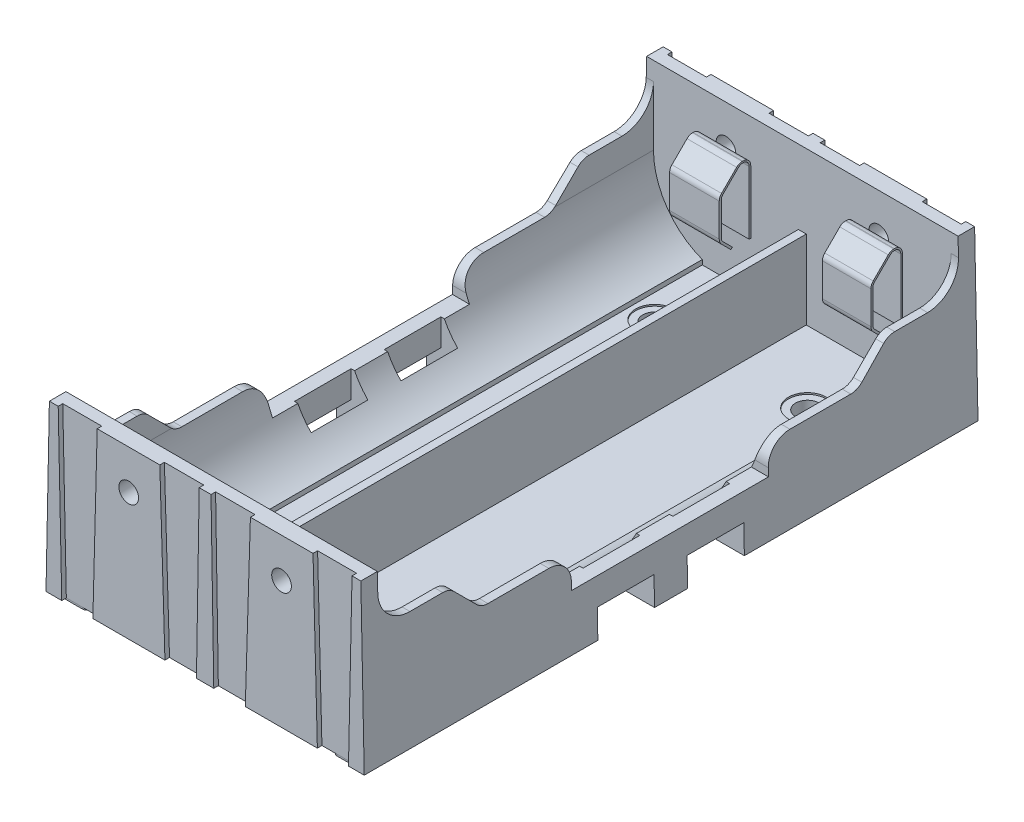
SolidWorks part; units mm, degrees
ref_plane "Plan de face" through (0, 0, 0) normal (0, 0, 1) x (1, 0, 0)
ref_plane "Plan de dessus" through (0, 0, 0) normal (0, 1, 0) x (1, 0, 0)
ref_plane "Plan de droite" through (0, 0, 0) normal (1, 0, 0) x (0, 0, -1)
sketch "Esquisse1" plane through (0, 0, 0) normal (0, 0, 1) x (1, 0, 0)
  line L0 (-20.2, 0) -> (20.2, 0)
  line L1 (20.2, 0) -> (19.9, 14.8)
  line L2 (19.9, 14.8) -> (18.9, 14.8)
  line L3 (18.9, 14.8) -> (18.9, 11.2676)
  line L4 (12.7, 1.74) -> (0.5, 1.74)
  line L5 (0.5, 1.74) -> (0.5, 11.74)
  line L6 (0.5, 11.74) -> (-0.5, 11.74)
  line L7 (0, 11.74) -> (0, 0)
  line L8 (12.7, 9.965) -> (12.7, -2.9901) construction
  line L9 (-6.3412, 2.34) -> (28.9788, 2.34) construction
  line L10 (12.7, 2.34) -> (12.7, 1.74)
  line L11 (6.3412, 2.34) -> (-28.9788, 2.34) construction
  line L12 (-12.7, 9.965) -> (-12.7, -2.9901) construction
  line L13 (-12.7, 2.34) -> (-12.7, 1.74)
  line L14 (-0.5, 1.74) -> (-0.5, 11.74)
  line L15 (-12.7, 1.74) -> (-0.5, 1.74)
  line L16 (-18.9, 14.8) -> (-18.9, 11.2676)
  line L17 (-19.9, 14.8) -> (-18.9, 14.8)
  line L18 (-20.2, 0) -> (-19.9, 14.8)
  arc A0 (-12.7, 2.34) -> (-18.9, 11.2676) centre (-9.3724, 11.2676) cw
  arc A1 (12.7, 2.34) -> (18.9, 11.2676) centre (9.3724, 11.2676) ccw
  arc A2 (12.7, 2.34) -> (18.9, 11.2676) centre (9.3724, 11.2676) ccw
  arc A3 (-12.7, 2.34) -> (-18.9, 11.2676) centre (-9.3724, 11.2676) cw
  point P15 (12.7, 2.34)
  dimension "D7" = 14.8
  dimension "D1" = 10
  dimension "D2" = 1.74
  dimension "D3" = 0.5
  dimension "D4" = 20.2
  dimension "D5" = 1
  dimension "D6" = 19.9
  dimension "D8" = 12.2
  dimension "D9" = 0.6
extrude "Boss.-Extru.1" add sketch "Esquisse1" along normal blind 73.72 contours L13 A0 L16 L17 L18 L0 L7 L6 L14 L15 | A1 L10 L4 L5 L6 L7 L0 L1 L2 L3 region at (-19.7996, 7.3949, 0) region at (0.2504, 5.87, 0)
sketch "Esquisse2" plane through (0, 0, 73.72) normal (0, 0, 1) x (1, 0, 0)
  line L0 (-20.2, 0) -> (20.2, 0)
  line L1 (20.2, 0) -> (19.7715, 21.14)
  line L2 (19.7715, 21.14) -> (-19.7715, 21.14)
  line L3 (-19.7715, 21.14) -> (-20.2, 0)
  line L4 (-20.2, 0) -> (-19.9, 14.8) construction
  line L5 (20.2, 0) -> (19.9, 14.8) construction
  dimension "D1" = 21.14
extrude "Boss.-Extru.2" add sketch "Esquisse2" along normal blind 2.1
sketch "Esquisse3" plane through (0, 0, 0) normal (0, 0, -1) x (-1, 0, 0)
  line L0 (-20.2, 0) -> (20.2, 0)
  line L1 (20.2, 0) -> (19.7715, 21.14)
  line L2 (19.7715, 21.14) -> (-19.7715, 21.14)
  line L3 (-19.7715, 21.14) -> (-20.2, 0)
extrude "Boss.-Extru.3" add sketch "Esquisse3" along normal blind 2.1
fillet "Congé1" radius 4 4 edges
sketch "Esquisse4" plane through (0, 0, 0) normal (1, 0, 0) x (0, 0, -1)
  line L0 (-64.72, 14.8) -> (-60.72, 10.8)
  line L1 (-60.72, 10.8) -> (-49.36, 10.8)
  line L2 (-49.36, 10.8) -> (-49.36, 7)
  line L3 (-49.36, 7) -> (-24.36, 7)
  line L4 (-36.86, 0) -> (-36.86, 25.0916) construction
  line L5 (-75.82, 0) -> (2.1, 0) construction
  line L6 (-64.72, 14.8) -> (-9, 14.8)
  line L7 (-69.72, 14.8) -> (-4, 14.8) construction
  line L8 (-73.72, 18.8) -> (-73.72, 21.14) construction
  line L9 (-24.36, 10.8) -> (-24.36, 7)
  line L10 (-13, 10.8) -> (-24.36, 10.8)
  line L11 (-9, 14.8) -> (-13, 10.8)
  point P15 (-36.86, 7)
  point P18 (-36.86, 14.8)
  dimension "D1" = 9
  dimension "D2" = 10.8
  dimension "D3" = 13
  dimension "D4" = 12.5
  dimension "D5" = 7
extrude "Enlèv. mat.-Extru.1" cut sketch "Esquisse4" against normal up to next and the other way through all from offset 20
extrude "Enlèv. mat.-Extru.2" cut sketch "Esquisse4<2>" along normal up to next from offset 30 offset against normal yes
sketch "Esquisse4<2>" plane through (0, 0, 0) normal (1, 0, 0) x (0, 0, -1) same geometry as "Esquisse4"
sketch "Esquisse6" plane through (0, 0, 0) normal (1, 0, 0) x (0, 0, -1)
  line L0 (-36.86, 0) -> (-36.86, 27.7538) construction
  line L1 (-46.16, -3.5482) -> (-38.96, -3.5482)
  line L2 (-46.16, -3.5482) -> (-46.16, 3.6)
  line L3 (-46.16, 3.6) -> (-38.96, 3.6)
  line L4 (-38.96, -3.5482) -> (-38.96, 3.6)
  line L5 (-75.82, 0) -> (2.1, 0) construction
  line L6 (-27.56, -3.5482) -> (-34.76, -3.5482)
  line L7 (-34.76, -3.5482) -> (-34.76, 3.6)
  line L8 (-27.56, 3.6) -> (-34.76, 3.6)
  line L9 (-27.56, -3.5482) -> (-27.56, 3.6)
  dimension "D1" = 7.2
  dimension "D2" = 4.2
  dimension "D3" = 3.6
extrude "Enlèv. mat.-Extru.3" cut sketch "Esquisse6" against normal blind 4 from vertex starting at point (20.2, 0, -2.1)
extrude "Enlèv. mat.-Extru.4" cut sketch "Esquisse6<2>" along normal blind 4 from vertex starting at point (-20.2, 0, -2.1)
sketch "Esquisse6<2>" plane through (0, 0, 0) normal (1, 0, 0) x (0, 0, -1) same geometry as "Esquisse6"
sketch "Esquisse7" plane through (0, 0, 0) normal (0, -1, 0) x (1, 0, 0)
  line L0 (0, 75.82) -> (0, 65.6835) construction
  line L1 (-20.2, 75.82) -> (20.2, 75.82) construction
  line L2 (0, 65.6835) -> (-20.2, 36.86) construction
  line L3 (-20.2, 38.96) -> (-20.2, 34.76) construction
  line L4 (-20.2, 36.86) -> (-7.0506, 36.86) construction
  line L5 (16.2, 38.96) -> (20.127, 38.96) construction
  line L6 (16.2, 46.16) -> (18.327, 46.16)
  line L7 (16.2, 46.16) -> (16.2, 38.96)
  line L8 (16.2, 38.96) -> (18.327, 38.96)
  line L9 (18.327, 46.16) -> (18.327, 38.96)
  line L10 (20.127, 46.16) -> (20.127, 38.96) construction
  line L11 (-18.327, 46.16) -> (-18.327, 38.96)
  line L12 (-16.2, 38.96) -> (-18.327, 38.96)
  line L13 (-16.2, 46.16) -> (-16.2, 38.96)
  line L14 (-16.2, 46.16) -> (-18.327, 46.16)
  line L15 (18.327, 27.56) -> (18.327, 34.76)
  line L16 (16.2, 34.76) -> (18.327, 34.76)
  line L17 (16.2, 27.56) -> (16.2, 34.76)
  line L18 (16.2, 27.56) -> (18.327, 27.56)
  line L19 (-16.2, 27.56) -> (-18.327, 27.56)
  line L20 (-16.2, 27.56) -> (-16.2, 34.76)
  line L21 (-16.2, 34.76) -> (-18.327, 34.76)
  line L22 (-18.327, 27.56) -> (-18.327, 34.76)
  dimension "D1" = 1.8
extrude "Enlèv. mat.-Extru.5" cut sketch "Esquisse7" against normal through all
fillet "Congé2" radius 2 8 edges at (-19.4, 14.8, 9) (19.4, 14.8, 9) (19.4, 14.8, 64.72) (-19.4, 14.8, 64.72) (-19.4348, 10.8, 60.72) (19.4348, 10.8, 60.72) (19.4348, 10.8, 13) (-19.4348, 10.8, 13)
fillet "Congé3" radius 2.8 4 edges at (19.4348, 10.8, 49.36) (19.4348, 10.8, 24.36) (-19.4348, 10.8, 24.36) (-19.4348, 10.8, 49.36)
sketch "Esquisse8" plane through (0, 0, 0) normal (0, -1, 0) x (1, 0, 0)
  line L0 (0, 75.82) -> (0, 59.6199) construction
  line L1 (-20.2, 75.82) -> (20.2, 75.82) construction
  line L2 (0, 59.6199) -> (-20.2, 36.86) construction
  line L3 (-20.2, 38.96) -> (-20.2, 34.76) construction
  line L4 (-20.2, 36.86) -> (-10.1, 36.86) construction
  line L5 (-20.2, 75.82) -> (-20.2, 46.16) construction
  line L6 (-19.1, 75.22) -> (-16.16, 75.22)
  line L7 (-19.6, 74.72) -> (-19.6, 73.42)
  line L8 (18.6, 73.42) -> (18.6, 74.12)
  line L9 (16.16, 74.22) -> (18.5, 74.22)
  line L10 (19.6, 74.72) -> (19.6, 73.42)
  line L11 (19.1, 75.22) -> (16.16, 75.22)
  line L12 (-16.16, 74.22) -> (-18.5, 74.22)
  line L13 (-18.6, 73.42) -> (-18.6, 74.12)
  line L14 (19.1, -1.5) -> (16.16, -1.5)
  line L15 (19.6, -1) -> (19.6, 0.3)
  line L16 (16.16, -0.5) -> (18.5, -0.5)
  line L17 (18.6, 0.3) -> (18.6, -0.4)
  line L18 (-18.6, 0.3) -> (-18.6, -0.4)
  line L19 (-16.16, -0.5) -> (-18.5, -0.5)
  line L20 (-19.6, -1) -> (-19.6, 0.3)
  line L21 (-19.1, -1.5) -> (-16.16, -1.5)
  circle A0 centre (-9.7, 64.66) radius 3
  circle A1 centre (9.7, 64.66) radius 3
  circle A2 centre (9.7, 9.06) radius 3
  circle A3 centre (-9.7, 9.06) radius 3
  arc A4 (-19.1, 75.22) -> (-19.6, 74.72) centre (-19.1, 74.72) ccw
  arc A5 (-19.6, 73.42) -> (-18.6, 73.42) centre (-19.1, 73.42) ccw
  arc A6 (-18.5, 74.22) -> (-18.6, 74.12) centre (-18.5, 74.12) ccw
  arc A7 (16.16, 74.22) -> (16.16, 75.22) centre (16.16, 74.72) cw
  arc A8 (18.5, 74.22) -> (18.6, 74.12) centre (18.5, 74.12) cw
  arc A9 (-16.16, 74.22) -> (-16.16, 75.22) centre (-16.16, 74.72) ccw
  arc A10 (19.6, 73.42) -> (18.6, 73.42) centre (19.1, 73.42) cw
  arc A11 (19.1, 75.22) -> (19.6, 74.72) centre (19.1, 74.72) cw
  arc A12 (19.1, -1.5) -> (19.6, -1) centre (19.1, -1) ccw
  arc A13 (19.6, 0.3) -> (18.6, 0.3) centre (19.1, 0.3) ccw
  arc A14 (18.5, -0.5) -> (18.6, -0.4) centre (18.5, -0.4) ccw
  arc A15 (16.16, -0.5) -> (16.16, -1.5) centre (16.16, -1) ccw
  arc A16 (-16.16, -0.5) -> (-16.16, -1.5) centre (-16.16, -1) cw
  arc A17 (-18.5, -0.5) -> (-18.6, -0.4) centre (-18.5, -0.4) cw
  arc A18 (-19.6, 0.3) -> (-18.6, 0.3) centre (-19.1, 0.3) cw
  arc A19 (-19.1, -1.5) -> (-19.6, -1) centre (-19.1, -1) cw
  dimension "D1" = 6
  dimension "D10" = 1
  dimension "D11" = 1
  dimension "D15" = 1
  dimension "D8" = 0.2
  dimension "D2" = 19.4
  dimension "D3" = 55.6
  dimension "D4" = 0.6
  dimension "D5" = 0.6
  dimension "D6" = 1
  dimension "D7" = 1
extrude "Boss.-Extru.4" add sketch "Esquisse8" along normal blind 0.22
sketch "Esquisse9" plane through (0, -0.22, 0) normal (0, -1, 0) x (-1, 0, 0)
  line L0 (0, -75.82) -> (0, -71.6703) construction
  line L1 (20.2, -75.82) -> (-20.2, -75.82) construction
  line L2 (0, -71.6703) -> (20.2, -36.86) construction
  line L3 (20.2, -38.96) -> (20.2, -34.76) construction
  line L4 (20.2, -36.86) -> (5.6708, -36.86) construction
  circle A0 centre (9.7, -64.66) radius 1.5
  circle A1 centre (9.7, -64.66) radius 3 construction
  circle A2 centre (-9.7, -64.66) radius 1.5
  circle A3 centre (-9.7, -9.06) radius 1.5
  circle A4 centre (9.7, -9.06) radius 1.5
  dimension "D1" = 3
extrude "Enlèv. mat.-Extru.6" cut sketch "Esquisse9" against normal through all
sketch "Esquisse10" plane through (0, 0, 75.82) normal (0, 0, 1) x (1, 0, 0)
  line L0 (-0.75, 21.14) -> (-1.1, 0)
  line L1 (-5.75, 21.14) -> (-5.1, 0)
  line L2 (-18.65, 21.14) -> (-18.2, 0)
  line L3 (-14.25, 0) -> (-13.7, 21.14)
  line L4 (0, 0) -> (0, 25.4346) construction
  line L5 (-18.65, 21.14) -> (-13.7, 21.14)
  line L6 (-18.2, 0) -> (-14.25, 0)
  line L7 (-5.75, 21.14) -> (-0.75, 21.14)
  line L8 (-5.1, 0) -> (-1.1, 0)
  line L9 (5.1, 0) -> (1.1, 0)
  line L10 (5.75, 21.14) -> (0.75, 21.14)
  line L11 (18.2, 0) -> (14.25, 0)
  line L12 (18.65, 21.14) -> (13.7, 21.14)
  line L13 (14.25, 0) -> (13.7, 21.14)
  line L14 (18.65, 21.14) -> (18.2, 0)
  line L15 (5.75, 21.14) -> (5.1, 0)
  line L16 (0.75, 21.14) -> (1.1, 0)
  dimension "D1" = 2.2
  dimension "D2" = 1.5
  dimension "D3" = 10.2
  dimension "D4" = 11.5
  dimension "D5" = 27.4
  dimension "D6" = 28.5
  dimension "D7" = 36.4
  dimension "D8" = 37.3
extrude "Enlèv. mat.-Extru.7" cut sketch "Esquisse10" against normal blind 0.58
extrude "Enlèv. mat.-Extru.8" cut sketch "Esquisse10<2>" along normal blind 0.58 from vertex starting at point (-20.2, 0, -2.1)
sketch "Esquisse10<2>" plane through (0, 0, 75.82) normal (0, 0, 1) x (1, 0, 0) same geometry as "Esquisse10"
sketch "Esquisse11" plane through (0, 1.74, 0) normal (0, 1, 0) x (1, 0, 0)
  circle A0 centre (-9.7, -9.06) radius 2.4
  circle A1 centre (9.7, -9.06) radius 2.4
  circle A2 centre (9.7, -64.66) radius 2.4
  circle A3 centre (-9.7, -64.66) radius 2.4
  dimension "D1" = 4.8
extrude "Enlèv. mat.-Extru.9" cut sketch "Esquisse11" against normal blind 0.2
sketch "Esquisse12" plane through (0, 1.74, 0) normal (0, 1, 0) x (1, 0, 0)
  line L0 (0, 2.1) -> (0, 19.1765) construction
  line L1 (-0.75, 2.1) -> (0.75, 2.1) construction
  line L3 (6.55, 0) -> (12.85, 0)
  line L4 (6.55, 0) -> (6.55, -4)
  line L5 (6.55, -4) -> (12.85, -4)
  line L6 (12.85, 0) -> (12.85, -4)
  line L7 (9.7, 0) -> (9.7, -4) construction
  line L8 (-19.7715, 0) -> (19.7715, 0) construction
  line L9 (-20.0581, -36.86) -> (-12.7, -36.86) construction
  line L10 (-20.0581, -24.36) -> (-20.0581, -49.36) construction
  line L11 (-12.7, -73.72) -> (-12.7, 0) construction
  line L12 (6.55, 0) -> (6.55, -4)
  line L13 (12.85, 0) -> (12.85, -4)
  line L14 (-9.7, 0) -> (-9.7, -4) construction
  line L15 (-12.85, 0) -> (-12.85, -4)
  line L16 (-6.55, 0) -> (-6.55, -4)
  line L17 (-12.85, 0) -> (-12.85, -4)
  line L18 (-6.55, -4) -> (-12.85, -4)
  line L19 (-6.55, 0) -> (-6.55, -4)
  line L20 (-6.55, 0) -> (-12.85, 0)
  line L21 (-9.7, -73.72) -> (-9.7, -69.72) construction
  line L22 (9.7, -73.72) -> (9.7, -69.72) construction
  line L23 (0, -75.82) -> (0, -92.8965) construction
  line L24 (-6.55, -73.72) -> (-12.85, -73.72)
  line L25 (-6.55, -73.72) -> (-6.55, -69.72)
  line L26 (-6.55, -69.72) -> (-12.85, -69.72)
  line L27 (-12.85, -73.72) -> (-12.85, -69.72)
  line L28 (-6.55, -73.72) -> (-6.55, -69.72)
  line L29 (-12.85, -73.72) -> (-12.85, -69.72)
  line L30 (12.85, -73.72) -> (12.85, -69.72)
  line L31 (6.55, -73.72) -> (6.55, -69.72)
  line L32 (12.85, -73.72) -> (12.85, -69.72)
  line L33 (6.55, -69.72) -> (12.85, -69.72)
  line L34 (6.55, -73.72) -> (6.55, -69.72)
  line L35 (6.55, -73.72) -> (12.85, -73.72)
  line M3 (12.7, 0) -> (0.5, 0)
  line M5 (0.5, -73.72) -> (12.7, -73.72)
  line M6 (12.7, -73.72) -> (12.7, 0)
  dimension "D1" = 6.3
  dimension "D2" = 9.7
  dimension "D3" = 4
extrude "Boss.-Extru.5" add sketch "Esquisse12" along normal blind 9 from offset 6 contours L27 L24 L25 L26 | L33 L31 M5 M6 | L4 L5 M6 M3 | L16 L20 L15 L18 region at (9.625, 1.74, 71.72) region at (9.625, 1.74, 2) region at (-9.7, 1.74, 2) region at (-9.7, 1.74, 71.72)
chamfer "Chanfrein1" distance 2.5 angle 45 4 edges at (-9.7, 16.74, 4) (9.625, 16.74, 4) (9.625, 16.74, 69.72) (-9.7, 16.74, 69.72)
chamfer "Chanfrein2" distance 1.5 angle 45 4 edges at (9.625, 7.74, 4) (-9.7, 7.74, 4) (-9.7, 7.74, 69.72) (9.625, 7.74, 69.72)
fillet "Congé4" radius 1 12 edges at (9.625, 9.24, 4) (9.625, 14.24, 4) (9.625, 16.74, 1.5) (-9.7, 9.24, 4) (-9.7, 14.24, 4) (-9.7, 16.74, 1.5) (-9.7, 9.24, 69.72) (-9.7, 14.24, 69.72) (-9.7, 16.74, 72.22) (9.625, 9.24, 69.72) (9.625, 14.24, 69.72) (9.625, 16.74, 72.22)
sketch "Esquisse13" plane through (12.7, 0, 0) normal (1, 0, 0) x (0, 0, -1)
  line L0 (-73.72, 16.74) -> (-72.6342, 16.74) construction
  line L1 (-73.72, 18.8) -> (-73.72, 11.2676) construction
  line L2 (-72.72, 16.74) -> (-72.72, 17.106)
  line L3 (-72.72, 17.106) -> (-73.72, 17.106)
  line L4 (-73.72, 17.106) -> (-73.72, 15.74)
  line L5 (-70.1972, 14.3486) -> (-72.1543, 16.3057)
  line L6 (-70.0129, 14.5329) -> (-71.9271, 16.4471) construction
  line L7 (-69.9807, 13.8258) -> (-69.9807, 9.6542)
  line L8 (-71.3853, 7.9433) -> (-70.1972, 9.1314)
  line L9 (-71.22, 7.74) -> (-70.0129, 8.9471) construction
  line L10 (-69.72, 13.8258) -> (-69.72, 9.6542) construction
  line L11 (-71.3853, 7.9433) -> (-70.8706, 7.4286)
  line L12 (-70.8706, 7.4286) -> (-72.5536, 6.5351)
  line L13 (-73.52, 15.74) -> (-73.52, 6.5351)
  line L15 (-73.52, 6.5351) -> (-72.5536, 6.5351)
  line L16 (-36.86, 0) -> (-36.86, 25.4697) construction
  line L17 (-38.96, 0) -> (-34.76, 0) construction
  line L18 (-0.2, 6.5351) -> (-1.1664, 6.5351)
  line L19 (-0.2, 15.74) -> (-0.2, 6.5351)
  line L20 (-2.8494, 7.4286) -> (-1.1664, 6.5351)
  line L21 (-2.3347, 7.9433) -> (-2.8494, 7.4286)
  line L22 (-2.3347, 7.9433) -> (-3.5228, 9.1314)
  line L23 (-3.7393, 13.8258) -> (-3.7393, 9.6542)
  line L24 (-3.5228, 14.3486) -> (-1.5657, 16.3057)
  line L25 (0, 17.106) -> (0, 15.74)
  line L26 (-1, 17.106) -> (0, 17.106)
  line L27 (-1, 16.74) -> (-1, 17.106)
  arc A0 (-72.72, 16.74) -> (-73.72, 15.74) centre (-72.72, 15.74) ccw
  arc A1 (-71.9271, 16.4471) -> (-72.6342, 16.74) centre (-72.6342, 15.74) ccw construction
  arc A2 (-72.1543, 16.3057) -> (-73.52, 15.74) centre (-72.72, 15.74) ccw
  arc A3 (-69.9807, 13.8258) -> (-70.1972, 14.3486) centre (-70.72, 13.8258) ccw
  arc A4 (-69.72, 13.8258) -> (-70.0129, 14.5329) centre (-70.72, 13.8258) ccw construction
  arc A5 (-70.1972, 9.1314) -> (-69.9807, 9.6542) centre (-70.72, 9.6542) ccw
  arc A7 (-70.0129, 8.9471) -> (-69.72, 9.6542) centre (-70.72, 9.6542) ccw construction
  arc A8 (-3.5228, 9.1314) -> (-3.7393, 9.6542) centre (-3, 9.6542) cw
  arc A9 (-3.7393, 13.8258) -> (-3.5228, 14.3486) centre (-3, 13.8258) cw
  arc A10 (-1.5657, 16.3057) -> (-0.2, 15.74) centre (-1, 15.74) cw
  arc A11 (-1, 16.74) -> (0, 15.74) centre (-1, 15.74) cw
  dimension "D1" = 0.2
extrude "Enlèv. mat.-Extru.10" cut sketch "Esquisse13" against normal up to next
extrude "Enlèv. mat.-Extru.11" cut sketch "Esquisse13<3>" against normal up to next from vertex starting at point (-6.55, 16.74, 0)
sketch "Esquisse13<3>" plane through (12.7, 0, 0) normal (1, 0, 0) x (0, 0, -1) same geometry as "Esquisse13"
sketch "Esquisse14" plane through (0, 0, -2.1) normal (0, 0, -1) x (-1, 0, 0)
  line L0 (13.7, 21.14) -> (5.75, 21.14) construction
  line L1 (0, 0) -> (0, 5.0643) construction
  line L2 (-1.1, 0) -> (1.1, 0) construction
  circle A0 centre (9.7, 16.14) radius 1.25
  circle A1 centre (-9.7, 16.14) radius 1.25
  dimension "D1" = 2.5
  dimension "D2" = 5
  dimension "D3" = 9.7
extrude "Enlèv. mat.-Extru.12" cut sketch "Esquisse14" against normal up to surface (2.1 mm away) up to face at (-9.7, 11.74, 0)
extrude "Enlèv. mat.-Extru.13" cut sketch "Esquisse14<2>" along normal up to surface (-75.82 mm away) from vertex up to face at (-9.7, 11.74, 73.72) starting at point (5.1, 0, 75.82)
sketch "Esquisse14<2>" plane through (0, 0, -2.1) normal (0, 0, -1) x (-1, 0, 0) same geometry as "Esquisse14"
